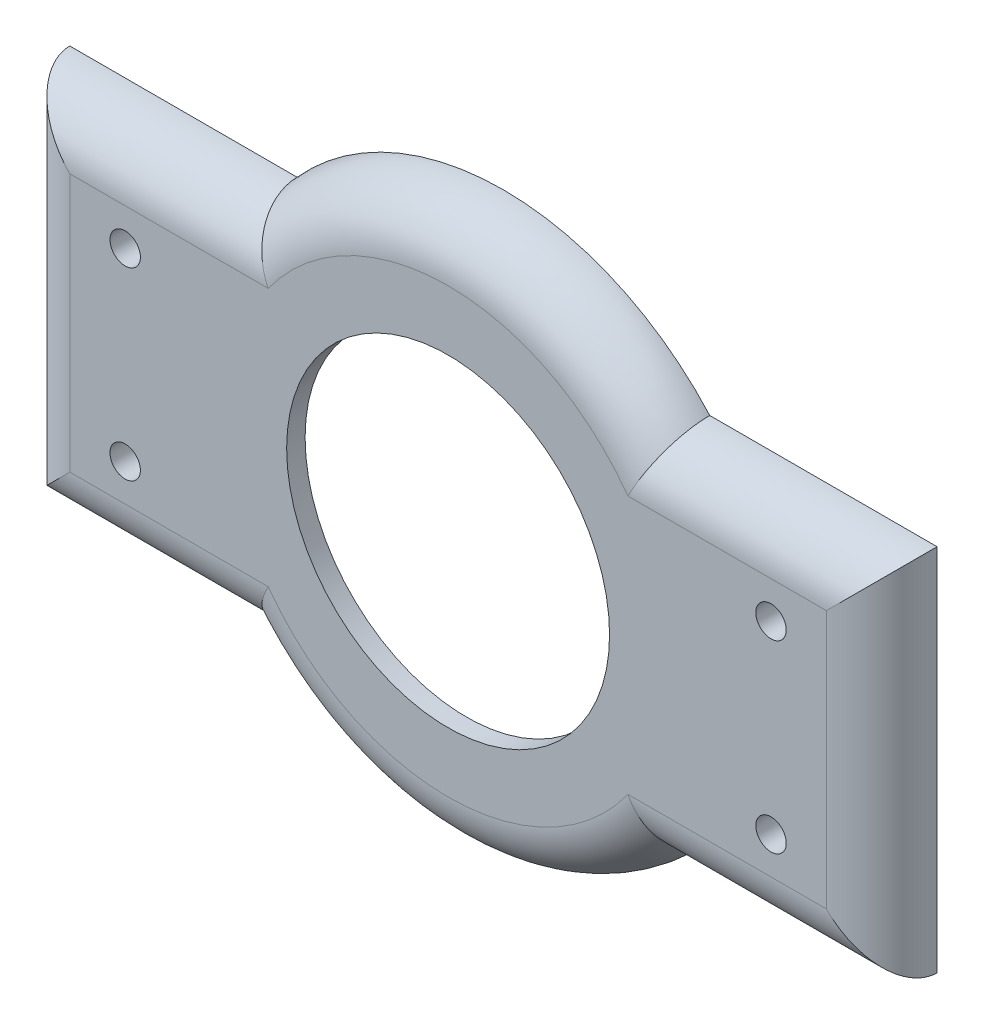
SolidWorks part; units mm, degrees
material "6061 Alloy"
ref_plane "Front Plane" through (0, 0, 0) normal (0, 0, 1) x (1, 0, 0)
ref_plane "Top Plane" through (0, 0, 0) normal (0, 1, 0) x (1, 0, 0)
ref_plane "Right Plane" through (0, 0, 0) normal (1, 0, 0) x (0, 0, -1)
sketch "Sketch1" plane through (0, 0, 0) normal (0, 0, 1) x (1, 0, 0)
  circle A0 centre (0, 0) radius 30
  dimension "D1" = 60
extrude "Boss-Extrude1" add sketch "Sketch1" along normal blind 2
sketch "Sketch2" plane through (0, 0, 0) normal (0, 0, -1) x (-1, 0, 0)
  circle A0 centre (0, 0) radius 25
  circle A1 centre (0, 0) radius 30
  dimension "D1" = 50
  dimension "D2" = 60
extrude "Boss-Extrude2" add sketch "Sketch2" along normal blind 4
sketch "Sketch3" plane through (0, 0, -4) normal (0, 0, -1) x (-1, 0, 0)
  line L1 (-47, -20) -> (47, -20)
  line L2 (-47, -20) -> (-47, 20)
  line L3 (-47, 20) -> (47, 20)
  line L4 (47, -20) -> (47, 20)
  line L5 (-47, -20) -> (47, 20) construction
  line L6 (-47, 20) -> (47, -20) construction
  point P0 (0, 0)
  dimension "D1" = 40
  dimension "D2" = 47
extrude "Boss-Extrude3" add sketch "Sketch3" against normal up to surface (6 mm away) up to face at (30, 0, 2)
sketch "Sketch4" plane through (0, 0, -4) normal (0, 0, -1) x (-1, 0, 0)
  circle A0 centre (0, 0) radius 25
  dimension "D1" = 50
extrude "Cut-Extrude1" cut sketch "Sketch4" against normal up to surface (4 mm away) up to face at (0, 22.5, 0)
sketch "Sketch5" plane through (0, 0, 0) normal (0, 0, -1) x (-1, 0, 0)
  circle A0 centre (0, 0) radius 17.5
  dimension "D1" = 35
extrude "Cut-Extrude2" cut sketch "Sketch5" against normal through all
fillet "Fillet1" radius 6 8 edges at (47, 0, 2) (34.6803, -20, 2) (34.6803, 20, 2) (0, 30, 2) (0, -30, 2) (-34.6803, -20, 2) (-47, 0, 2) (-34.6803, 20, 2)
hole_wizard "M4x0.7 Tapped Hole1" positions "Sketch6" profile "Sketch7" tap size "M4x0.7" standard "ANSI Metric" end condition through all
sketch "Sketch6" plane through (0, 0, 2) normal (0, 0, 1) x (1, 0, 0)
  point P0 (-35, 10)
  point P2 (-35, -10)
  point P4 (35, 10)
  point P6 (35, -10)
  dimension "D1" = 35
  dimension "D2" = 35
  dimension "D3" = 10
  dimension "D4" = 10
sketch "Sketch7" plane through (-35, 10, 2) normal (1, 0, 0) x (0, -1, 0)
  line L0 (0, 0) -> (0, 6.3265)
  line L1 (0, 6.3265) -> (1.65, 6.3265)
  line L2 (1.65, 6.3265) -> (1.65, 0)
  line L5 (1.65, 0) -> (0, 0)
  line L11 (0, -6.35) -> (0, 107.95) construction
  dimension "Thru Tap Drill Dia." = 3.3
  dimension "Thru Tap Drill Depth" = 6.3265
cosmetic thread "Hole Thread1" parameters "D2"=4
cosmetic thread "Hole Thread2" parameters "D2"=4
cosmetic thread "Hole Thread3" parameters "D2"=4
cosmetic thread "Hole Thread4" parameters "D2"=4
